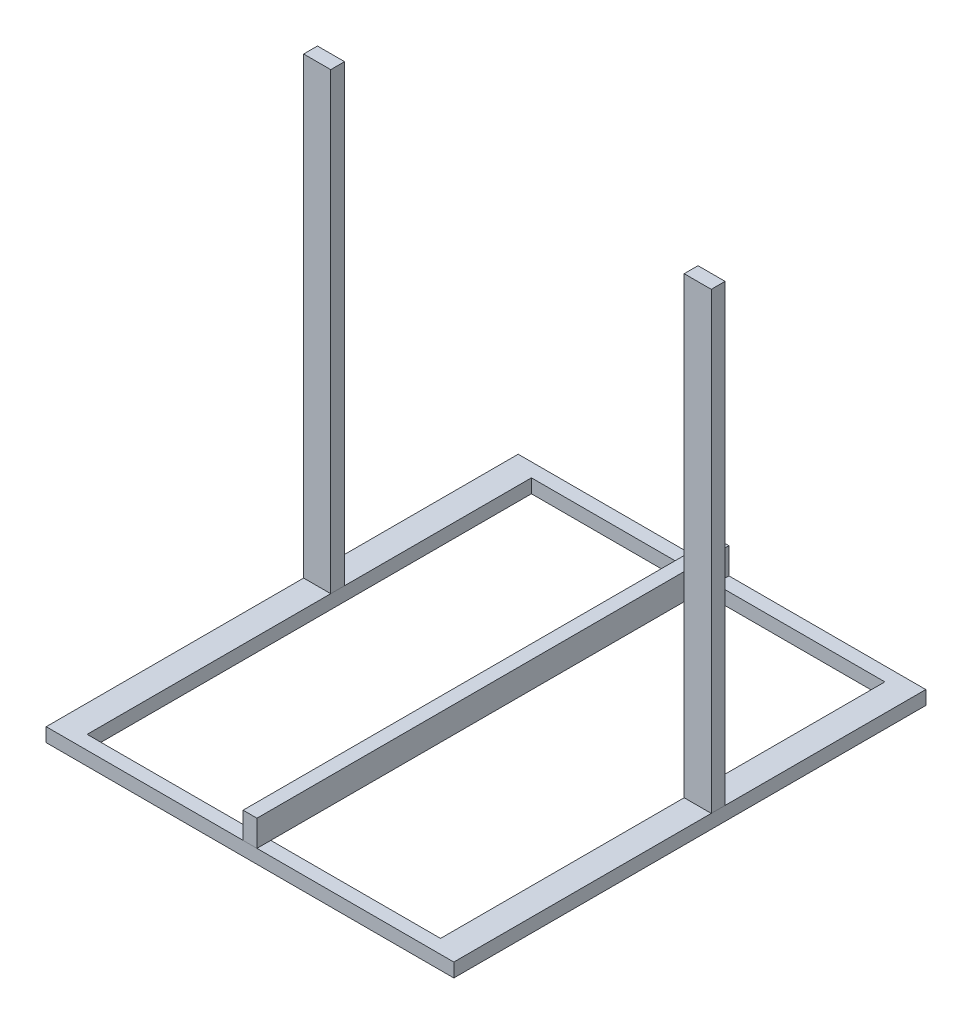
SolidWorks part; units mm, degrees
material "6061 Alloy"
ref_plane "Front Plane" through (0, 0, 0) normal (0, 0, 1) x (1, 0, 0)
ref_plane "Top Plane" through (0, 0, 0) normal (0, 1, 0) x (1, 0, 0)
ref_plane "Right Plane" through (0, 0, 0) normal (1, 0, 0) x (0, 0, -1)
sketch "Sketch1" plane through (0, 0, 0) normal (0, 1, 0) x (1, 0, 0)
  line L1 (-301.625, -349.25) -> (301.625, -349.25)
  line L2 (-301.625, -349.25) -> (-301.625, 349.25)
  line L3 (-301.625, 349.25) -> (301.625, 349.25)
  line L4 (301.625, -349.25) -> (301.625, 349.25)
  line L5 (-301.625, -349.25) -> (301.625, 349.25) construction
  line L6 (-301.625, 349.25) -> (301.625, -349.25) construction
  line L7 (261.525, 328.78) -> (-261.525, 328.78)
  line L8 (261.525, 328.78) -> (261.525, -328.78)
  line L9 (261.525, -328.78) -> (-261.525, -328.78)
  line L10 (-261.525, 328.78) -> (-261.525, -328.78)
  line L11 (261.525, 328.78) -> (-261.525, -328.78) construction
  line L12 (261.525, -328.78) -> (-261.525, 328.78) construction
  point P0 (0, 0)
  point P6 (0, 0)
  dimension "D1" = 603.25
  dimension "D2" = 698.5
  dimension "D3" = 20.47
  dimension "D4" = 40.1
extrude "Boss-Extrude1" add sketch "Sketch1" along normal blind 20.47
sketch "Sketch2" plane through (0, 20.47, 0) normal (0, 1, 0) x (1, 0, 0)
  line L0 (-301.625, 349.25) -> (-301.625, -349.25) construction
  line L1 (-261.525, 52.22) -> (-301.625, 52.22)
  line L2 (-261.525, 52.22) -> (-261.525, 31.75)
  line L3 (-261.525, 31.75) -> (-301.625, 31.75)
  line L4 (-301.625, 52.22) -> (-301.625, 31.75)
  line L5 (-261.525, 52.22) -> (-301.625, 31.75) construction
  line L6 (-261.525, 31.75) -> (-301.625, 52.22) construction
  line L7 (261.525, -328.78) -> (261.525, 328.78) construction
  line L8 (301.625, 52.22) -> (261.525, 52.22)
  line L9 (301.625, 52.22) -> (301.625, 31.75)
  line L10 (301.625, 31.75) -> (261.525, 31.75)
  line L11 (261.525, 52.22) -> (261.525, 31.75)
  line L12 (301.625, 52.22) -> (261.525, 31.75) construction
  line L13 (301.625, 31.75) -> (261.525, 52.22) construction
  line L14 (301.625, -349.25) -> (301.625, 349.25) construction
  line L15 (-261.525, 328.78) -> (-261.525, -328.78) construction
  line L16 (-301.625, -349.25) -> (301.625, -349.25) construction
  point P0 (-281.575, 41.985)
  point P7 (281.575, 41.985)
  dimension "D1" = 20.47
  dimension "D2" = 381
extrude "Boss-Extrude2" add sketch "Sketch2" along normal blind 671.68
sketch "Sketch3" plane through (0, 20.47, 0) normal (0, 1, 0) x (1, 0, 0)
  line L0 (-301.625, -349.25) -> (301.625, -349.25) construction
  line L1 (-10.27, 349.25) -> (10.27, 349.25)
  line L2 (-10.27, 349.25) -> (-10.27, -349.25)
  line L3 (-10.27, -349.25) -> (10.27, -349.25)
  line L4 (10.27, 349.25) -> (10.27, -349.25)
  line L5 (-10.27, 349.25) -> (10.27, -349.25) construction
  line L6 (-10.27, -349.25) -> (10.27, 349.25) construction
  point P0 (0, 0)
  dimension "D1" = 20.54
extrude "Boss-Extrude3" add sketch "Sketch3" along normal blind 38.67
sketch "Sketch4" plane through (0, 20.47, 0) normal (0, 1, 0) x (1, 0, 0)
  line L1 (-301.625, 52.22) -> (-261.525, 52.22)
  line L2 (-301.625, 52.22) -> (-301.625, 31.75)
  line L3 (-301.625, 31.75) -> (-261.525, 31.75)
  line L4 (-261.525, 52.22) -> (-261.525, 31.75)
  line L5 (261.525, 52.22) -> (301.625, 52.22)
  line L6 (261.525, 52.22) -> (261.525, 31.75)
  line L7 (261.525, 31.75) -> (301.625, 31.75)
  line L8 (301.625, 52.22) -> (301.625, 31.75)
split "Split1" bodies to split 103 resulting bodies 104 105 106 107 split by face at (-191.14, 20.47, 215.4267)
